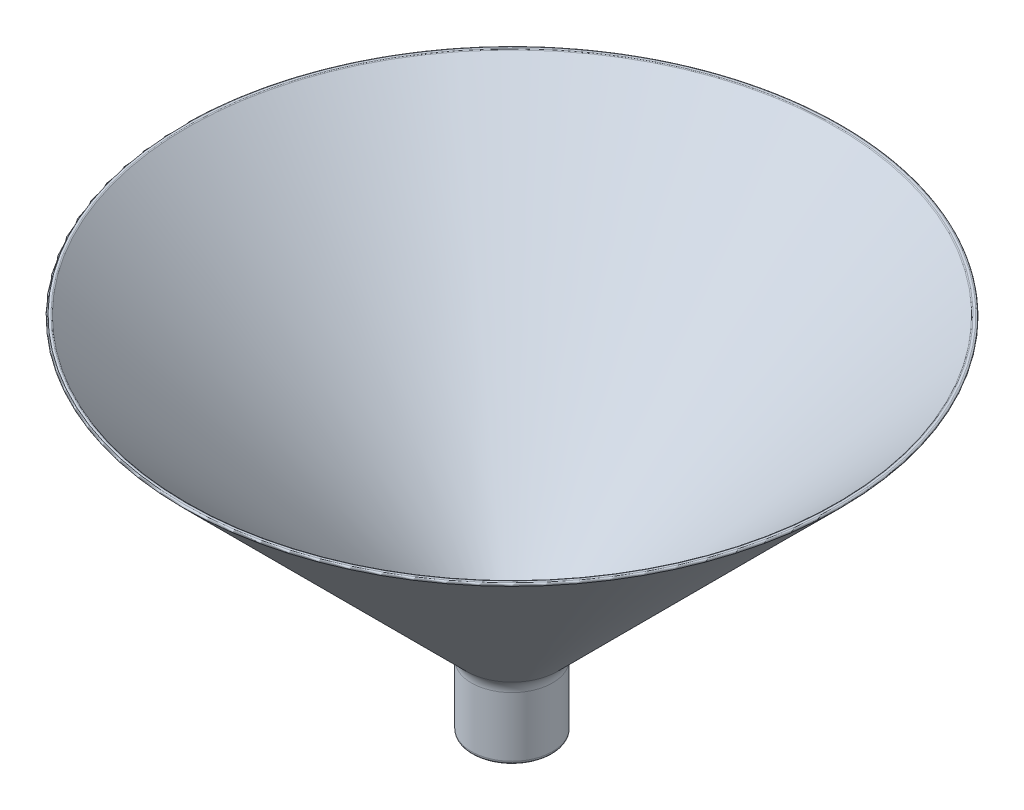
SolidWorks part; units mm, degrees
ref_plane "Front Plane" through (0, 0, 0) normal (0, 0, 1) x (1, 0, 0)
ref_plane "Top Plane" through (0, 0, 0) normal (0, 1, 0) x (1, 0, 0)
ref_plane "Right Plane" through (0, 0, 0) normal (1, 0, 0) x (0, 0, -1)
sketch "Sketch1" plane through (0, 0, 0) normal (0, 0, 1) x (1, 0, 0)
  line L0 (0, 0) -> (6, 0) construction
  line L1 (10, 6.9282) -> (10, 20)
  line L2 (10, 20) -> (90, 100)
  line L3 (0, 0) -> (0, 100) construction
  line L7 (90, 100) -> (91.6971, 100)
  line L9 (6, 0) -> (10, 6.9282)
  line L10 (11.2, 6.6067) -> (11.2, 19.5029)
  line L11 (11.2, 19.5029) -> (91.6971, 100)
  line L12 (11.2, 19.5029) -> (90.4971, 98.8) construction
  line L13 (6, 0) -> (11.2, 0)
  line L14 (7.0392, -0.6) -> (11.2, 6.6067) construction
  line L15 (90.4971, 98.8) -> (91.6971, 98.8) construction
  line L16 (11.2, 6.6067) -> (11.2, 0)
  dimension "D1" = 10
  dimension "D2" = 20
  dimension "D3" = 135
  dimension "D4" = 100
  dimension "D6" = 6
  dimension "D7" = 60
  dimension "D5" = 1.2
revolve "Revolve1" add sketch "Sketch1" angle 360 about L3
fillet "Fillet1" radius 5 2 edges at (0, 19.5029, -11.2) (0, 20, -10)
fillet "Fillet2" radius 0.4 2 edges at (0, 100, -90) (0, 100, -91.6971)
fillet "Fillet3" radius 1 1 edges at (0, 0, -11.2)
